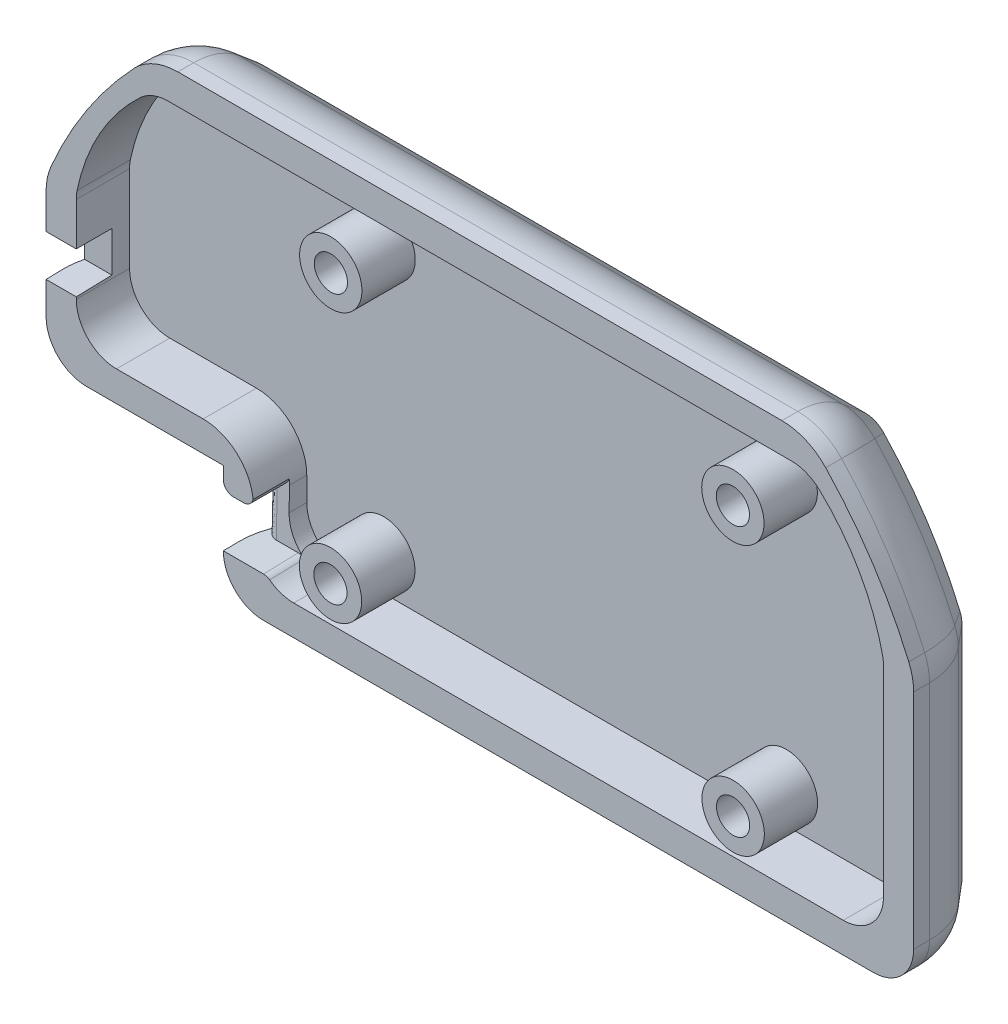
SolidWorks part; units mm, degrees
ref_plane "Alzado" through (0, 0, 0) normal (0, 0, 1) x (1, 0, 0)
ref_plane "Planta" through (0, 0, 0) normal (0, 1, 0) x (1, 0, 0)
ref_plane "Vista lateral" through (0, 0, 0) normal (1, 0, 0) x (0, 0, -1)
sketch "Croquis2" plane through (0, 0, 0) normal (0, 0, 1) x (1, 0, 0)
  line L0 (-43.6, 25.3285) -> (-43.6, 41.313)
  line L1 (-32.9688, 56.9561) -> (32.0312, 56.9561)
  line L2 (42.6624, 41.313) -> (42.6624, 25.3285)
  line L7 (-43.6, 25.3285) -> (-25.98, 25.3285)
  line L8 (-25.98, 25.3285) -> (-25.98, 13.9787)
  line L9 (-25.98, 13.9787) -> (42.6624, 13.9787)
  line L10 (42.6624, 13.9787) -> (42.6624, 25.3285)
  arc A0 (-43.6, 41.313) -> (-32.9688, 56.9561) centre (-3.7394, 25.6575) cw
  arc A1 (32.0312, 56.9561) -> (42.6624, 41.313) centre (2.8018, 25.6575) cw
  point P8 (0, 0)
extrude "Saliente-Extruir1" add sketch "Croquis2" along normal blind 8.3
sketch "Croquis3" plane through (0, 0, 8.3) normal (0, 0, 1) x (1, 0, 0)
  line L0 (39.6624, 41.313) -> (39.6624, 28.3285)
  line L1 (-40.6, 28.3285) -> (-22.98, 28.3285)
  line L2 (-40.6, 41.313) -> (-40.6, 28.3285)
  line L7 (-22.98, 28.3285) -> (-22.98, 16.9787)
  line L8 (-22.98, 16.9787) -> (39.6624, 16.9787)
  line L11 (39.6624, 16.9787) -> (39.6624, 28.3285)
  line L17 (-32.9688, 53.9561) -> (32.0312, 53.9561)
  arc A0 (-40.6, 41.313) -> (-32.9688, 53.9561) centre (-19.994, 37.5001) cw
  arc A1 (32.0312, 53.9561) -> (39.6624, 41.313) centre (18.518, 37.1752) cw
extrude "Cortar-Extruir1" cut sketch "Croquis3" against normal blind 5.3
fillet "Redondeo1" radius 4 10 edges at (39.6624, 16.9787, 5.65) (39.6624, 41.313, 5.65) (32.0312, 53.9561, 5.65) (-22.98, 16.9787, 5.65) (-40.6, 28.3285, 5.65) (-32.9688, 53.9561, 5.65) (-40.6, 41.313, 5.65) (42.6624, 13.9787, 4.15) (-25.98, 13.9787, 4.15) (-43.6, 25.3285, 4.15)
fillet "Redondeo2" radius 6 4 edges at (-43.6, 41.313, 4.15) (-32.9688, 56.9561, 4.15) (42.6624, 41.313, 4.15) (32.0312, 56.9561, 4.15)
chamfer "Chaflán1" distance 3.5 angle 50 15 edges at (31.9344, 56.4667, 0) (-0.4688, 56.9561, 0) (-32.872, 56.4667, 0) (-39.5452, 49.1503, 0) (-43.478, 41.3361, 0) (-43.6, 34.7305, 0) (-42.4285, 26.5001, 0) (-32.79, 25.3285, 0) (-25.98, 21.6536, 0) (-24.8085, 15.1503, 0) (8.3412, 13.9787, 0) (41.4908, 15.1503, 0) (42.6624, 29.0556, 0) (42.5404, 41.3361, 0) (38.6075, 49.1503, 0)
fillet "Redondeo3" radius 7 15 edges at (-42.4285, 26.5001, 4.1711) (-24.8085, 15.1503, 4.1711) (-32.79, 25.3285, 4.1711) (-25.98, 21.6536, 4.1711) (-43.6, 34.7305, 4.1711) (-43.478, 41.3361, 4.1711) (-39.5452, 49.1503, 4.1711) (-32.872, 56.4667, 4.1711) (31.9344, 56.4667, 4.1711) (-0.4688, 56.9561, 4.1711) (42.5404, 41.3361, 4.1711) (38.6075, 49.1503, 4.1711) (42.6624, 29.0556, 4.1711) (41.4908, 15.1503, 4.1711) (8.3412, 13.9787, 4.1711)
sketch "Croquis4" plane through (0, 0, 0) normal (0, 0, -1) x (-1, 0, 0)
  circle A4 centre (-24.7052, 47.2078) radius 2.775
  circle A5 centre (15.2948, 47.2217) radius 2.775
  circle A8 centre (-24.7009, 20.457) radius 2.775
  circle A9 centre (15.2996, 20.4717) radius 2.775
  point P0 (0, 0)
  dimension "D1" = 26.7508
  dimension "D2" = 26.75
extrude "Cortar-Extruir2" cut sketch "Croquis4" against normal blind 5
sketch "Croquis7" plane through (-23.5317, 0, -19.7454) normal (-0.766, 0, -0.6428) x (-0.6428, 0, 0.766)
sketch "Croquis8" plane through (-43.6, 0, 0) normal (-1, 0, 0) x (0, 0, 1)
  line L0 (8.5837, 36.6559) -> (8.5837, 32.5265)
  line L1 (4.7524, 36.6559) -> (4.7524, 32.6311)
  line L2 (4.7524, 36.6559) -> (8.5837, 36.6559)
  line L3 (4.7524, 32.6311) -> (8.5837, 32.5265)
  point P3 (0, 0)
  point P6 (0, 0)
  point P7 (0, 0)
extrude "Cortar-Extruir3" cut sketch "Croquis8" against normal blind 5
sketch "Croquis9" plane through (-25.98, 0, 0) normal (-1, 0, 0) x (0, 0, 1)
  line L0 (8.4088, 23.1178) -> (8.4088, 17.9733)
  line L1 (8.4088, 23.1178) -> (4.7271, 23.1178)
  line L2 (4.7271, 23.1178) -> (4.7935, 18.0212)
  line L3 (4.7935, 18.0212) -> (8.4088, 17.9733)
  point P4 (0, 0)
  point P5 (0, 0)
extrude "Cortar-Extruir6" cut sketch "Croquis9" against normal blind 7
fillet "Redondeo6" radius 1 4 edges at (-25.98, 23.1178, 7.5095) (-22.98, 23.1178, 6.5136) (-25.9073, 23.1178, 5.7126) (-21.6473, 17.9978, 6.5553)
fillet "Redondeo7" radius 1 1 edges at (-25.6985, 21.0721, 4.7538)
fillet "Redondeo8" radius 5 1 edges at (-22.98, 28.3285, 5.65)
sketch "Croquis12" plane through (0, 0, 3) normal (0, 0, 1) x (1, 0, 0)
  circle A1 centre (-15.2942, 47.2641) radius 3.1
  circle A2 centre (-15.281, 47.2434) radius 1.65
  circle A3 centre (-15.3273, 20.4744) radius 1.65
  circle A4 centre (-15.3188, 20.4913) radius 3.1
  circle A5 centre (24.7088, 20.4688) radius 1.65
  circle A6 centre (24.7151, 20.4625) radius 3.1
  circle A7 centre (24.6903, 47.2297) radius 1.65
  circle A8 centre (24.6903, 47.2179) radius 3.1
  point P0 (0, 0)
extrude "Saliente-Extruir4" add sketch "Croquis12" along normal up to surface (5.3 mm away) up to face at (-1.6529, 36.9174, 8.3)
